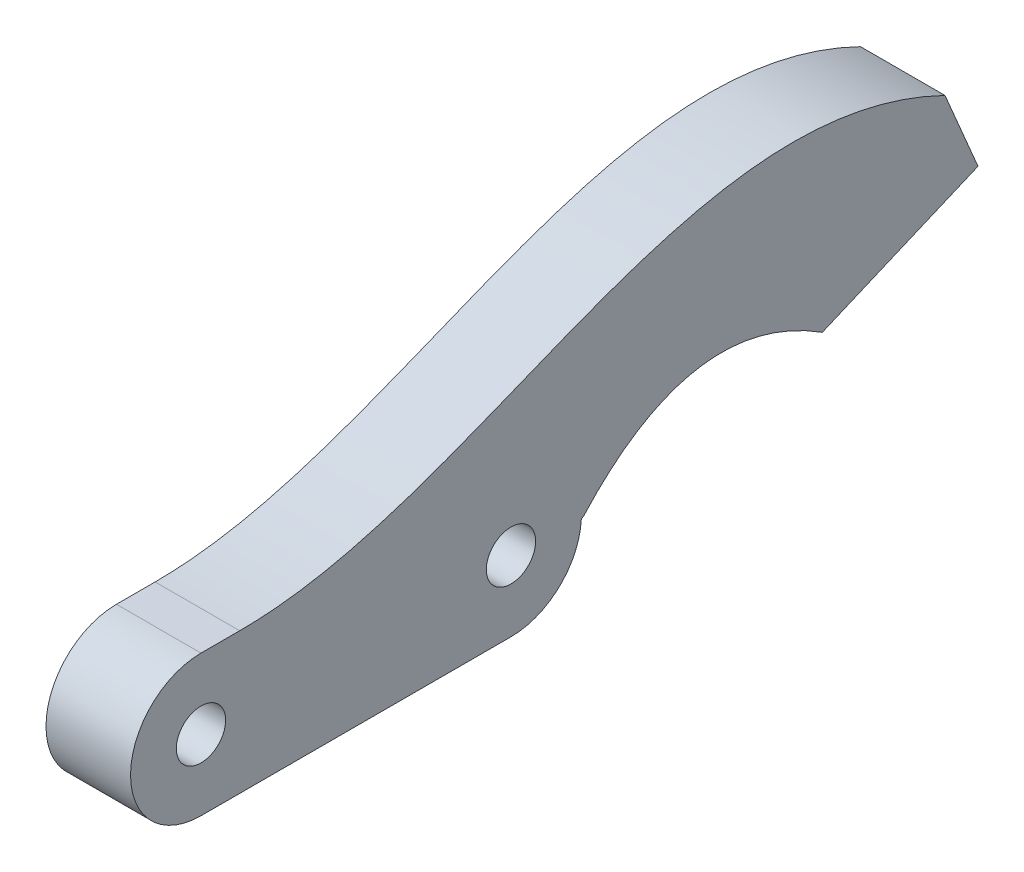
SolidWorks part; units mm, degrees
ref_plane "Front Plane" through (0, 0, 0) normal (0, 0, 1) x (1, 0, 0)
ref_plane "Top Plane" through (0, 0, 0) normal (0, 1, 0) x (1, 0, 0)
ref_plane "Right Plane" through (0, 0, 0) normal (1, 0, 0) x (0, 0, -1)
sketch "Sketch1" plane through (0, 0, 0) normal (1, 0, 0) x (0, 0, -1)
  line L1 (0, 0) -> (27, 0)
  line L2 (0, 0) -> (0, 10)
  line L3 (0, 10) -> (27, 10)
  circle A0 centre (5, 5) radius 1.75
  circle A1 centre (5, 5) radius 5
  circle A2 centre (27, 5) radius 5
  circle A3 centre (27, 5) radius 1.75
  dimension "D7" = 3.5
  dimension "D11" = 10
  dimension "D2" = 3.5
  dimension "D1" = 10
  dimension "D8" = 5
  dimension "D9" = 5
  dimension "D10" = 22
extrude "Boss-Extrude1" add sketch "Sketch1" along normal blind 6 contours A1 A0 | A2 L3 A1 L1 | A2 A3 | L2 A1 | L1 A1 region at (0, 5, -16) region at (0, 1.5645, -1.5645) region at (0, 5, -22.1414)
sketch "Sketch2" plane through (6, 0, 5.9488) normal (1, 0, 0) x (0, 0, -1)
  line L14 (5, 10) -> (27, 10)
  line L20 (29.1838, 0.5021) -> (38.0854, 4.8241)
  line L21 (55.0455, 7.6656) -> (66.0942, 12.3481)
  line L22 (66.0942, 12.3481) -> (63.753, 17.8724)
  arc A4 (27, 0) -> (27, 10) centre (27, 5) ccw
  spline S0 degree 2 poles (38.0854, 4.8241) (45.8792, 13.4817) (55.0455, 7.6656) knots 0 0 0 1 1 1
  spline S1 degree 3 poles (63.753, 17.8724) (45.9289, 26.5638) (31.0593, 10) (13.695, 10) knots 0 0 0 0 1 1 1 1
  point P2 (27, 5)
  line M1 (32.9488, 10) -> (10.9488, 10)
  arc M4 (32.9488, 0) -> (32.9488, 10) centre (32.9488, 5) ccw
  dimension "D3" = 6
  dimension "D4" = 12
extrude "Boss-Extrude2" add sketch "Sketch2" against normal blind 6 contours M1 M4 region at (6, 13.6614, -41.1043)
